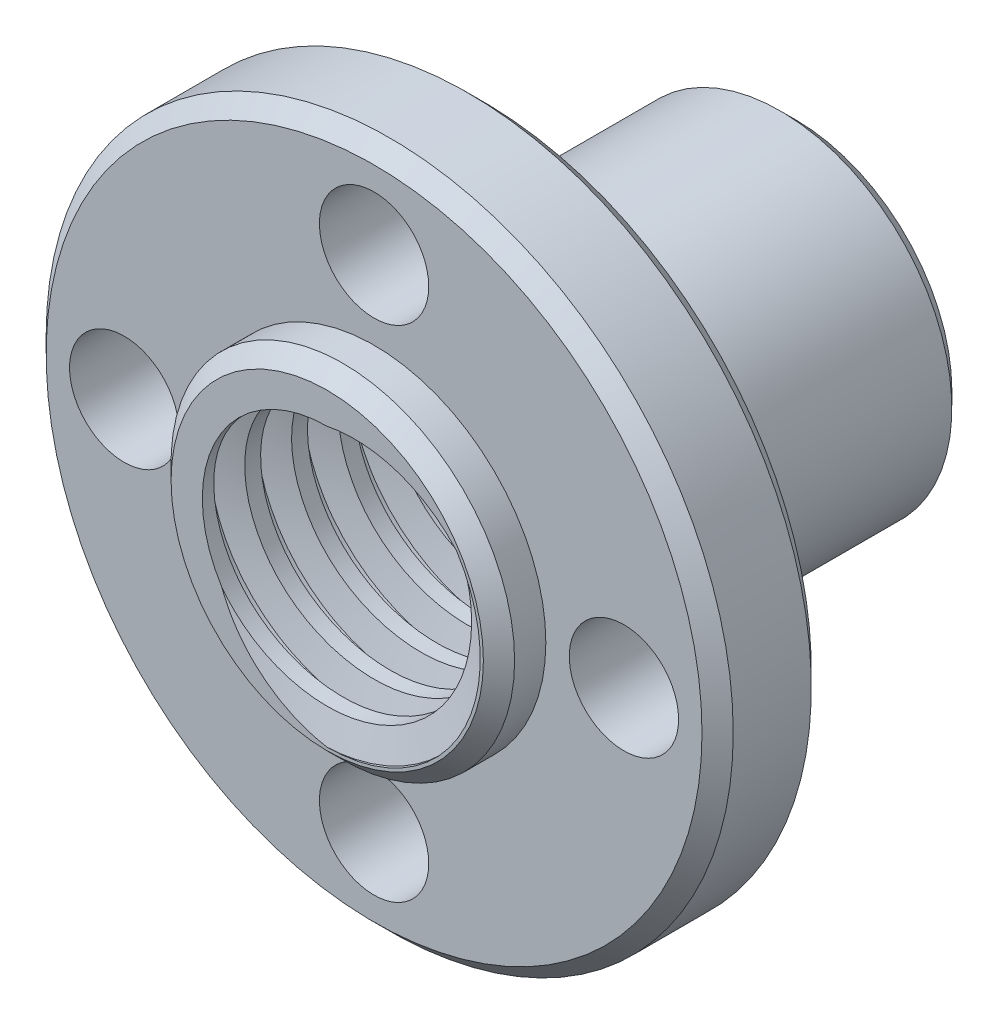
SolidWorks part; units mm, degrees
ref_plane "前视基准面" through (0, 0, 0) normal (0, 0, 1) x (1, 0, 0)
ref_plane "上视基准面" through (0, 0, 0) normal (0, 1, 0) x (1, 0, 0)
ref_plane "右视基准面" through (0, 0, 0) normal (1, 0, 0) x (0, 0, -1)
sketch "草图1" plane through (0, 0, 0) normal (1, 0, 0) x (0, 0, -1)
  line L0 (0, 0) -> (-9.8508, 0) construction
  line L1 (-15, 11) -> (0, 11)
  line L2 (-15, 11) -> (-15, 4)
  line L3 (-15, 4) -> (0, 4)
  line L4 (0, 11) -> (0, 4)
  dimension "bm" = 15
  dimension "d0" = 8
  dimension "dm" = 22
revolve "旋转1" add sketch "草图1" angle 360 about L0
sketch "草图2" plane through (0, 0, 0) normal (1, 0, 0) x (0, 0, -1)
  line L0 (0, 4) -> (0.9912, 4)
  line L1 (0, 4) -> (0.2412, 3.1) construction
  line L2 (0.2412, 3.1) -> (0.75, 3.1) construction
  line L3 (0.75, 3.1) -> (0.9912, 4) construction
  line L4 (-15, 4) -> (0, 4) construction
  line L5 (-15, 4) -> (0, 4) construction
  line L6 (0.75, 4.9) -> (0.9912, 4)
  line L7 (0.2412, 4.9) -> (0.75, 4.9)
  line L8 (0, 4) -> (0.2412, 4.9)
  dimension "t1" = 0.2412
  dimension "t2" = 0.5088
  dimension "p1" = 0.9912
  dimension "d1" = 3.1
sketch "草图3" plane through (0, 0, 0) normal (0, 0, 1) x (1, 0, 0)
  circle A0 centre (0, 0) radius 4
curve "螺旋线/涡状线1" pitch 1.5 height 30 turns 20 parameters "p"=1.5
sweep "切除-扫描1" cut profiles "草图2" path "螺旋线/涡状线1"
sketch "草图4" plane through (0, 0, 15) normal (0, 0, 1) x (1, 0, 0)
  circle A0 centre (0, 0) radius 5.5
  circle A1 centre (0, 0) radius 11 construction
  circle A2 centre (0, 0) radius 11
  dimension "D1" = 11
extrude "切除-拉伸1" cut sketch "草图4" against normal blind 1.5
sketch "草图5" plane through (0, 0, 0) normal (0, 0, -1) x (-1, 0, 0)
  circle A0 centre (0, 0) radius 5.5 construction
  circle A1 centre (0, 0) radius 11
  circle A2 centre (0, 0) radius 11
  circle A3 centre (0, 0) radius 5.5
  dimension "D1" = 0
extrude "切除-拉伸2" cut sketch "草图5" against normal blind 10
sketch "草图6" plane through (0, 0, 13.5) normal (0, 0, 1) x (1, 0, 0)
  circle A0 centre (0, 0) radius 8 construction
  circle A1 centre (0, 8) radius 1.75
  circle A2 centre (-8, 0) radius 1.75
  circle A3 centre (0, -8) radius 1.75
  circle A4 centre (8, 0) radius 1.75
  dimension "D1" = 16
  dimension "D2" = 3.5
extrude "切除-拉伸3" cut sketch "草图6" against normal through all
chamfer "倒角1" distance 0.5 angle 45 4 edges at (-5.5, 0, 0) (5.5, 0, 15) (-11, 0, 10) (11, 0, 13.5)
equation "\"p1@草图2\" = \"t1@草图2\" * 2 + \"t2@草图2\""
equation "\"p@螺旋线/涡状线1\" =  \"p1@草图2\" + \"t2@草图2\""
equation "\"n@螺旋线/涡状线1\" = \"bm@草图1\" / \"p@螺旋线/涡状线1\"*2"
